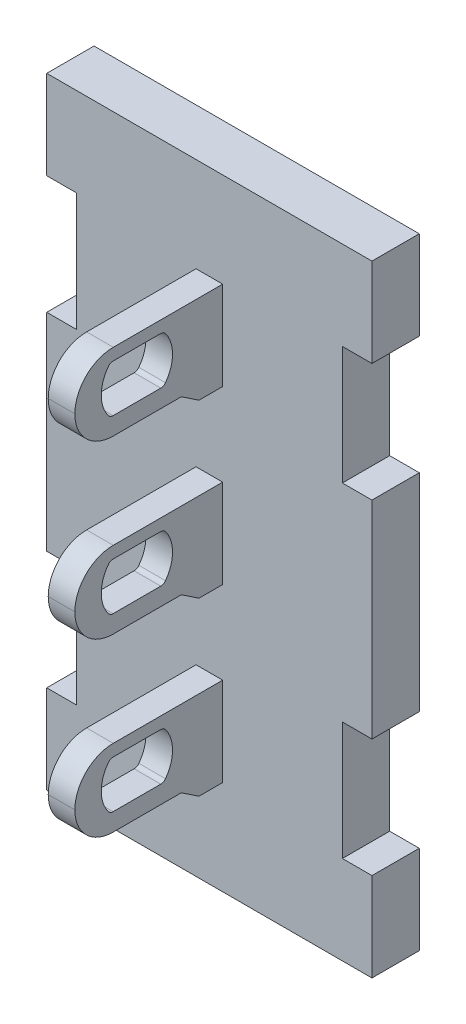
SolidWorks part; units mm, degrees
ref_plane "前视基准面" through (0, 0, 0) normal (0, 0, 1) x (1, 0, 0)
ref_plane "上视基准面" through (0, 0, 0) normal (0, 1, 0) x (1, 0, 0)
ref_plane "右视基准面" through (0, 0, 0) normal (1, 0, 0) x (0, 0, -1)
sketch "草图1" plane through (0, 0, 0) normal (0, 0, 1) x (1, 0, 0)
  line L1 (2.75, -5.25) -> (-2.75, -5.25)
  line L2 (2.75, -5.25) -> (2.75, 5.25)
  line L3 (2.75, 5.25) -> (-2.75, 5.25)
  line L4 (-2.75, -5.25) -> (-2.75, 5.25)
  line L5 (2.75, -5.25) -> (-2.75, 5.25) construction
  line L6 (2.75, 5.25) -> (-2.75, -5.25) construction
  point P0 (0, 0)
  dimension "D1" = 5.5
  dimension "D2" = 10.5
extrude "凸台-拉伸1" add sketch "草图1" along normal blind 0.8
sketch "草图2" plane through (0, 0, 0) normal (0, 0, -1) x (-1, 0, 0)
  line L0 (-2.75, -5.25) -> (-2.75, 5.25) construction
  line L1 (-2.25, 1.75) -> (-3.25, 1.75)
  line L2 (-2.25, 1.75) -> (-2.25, 3.75)
  line L3 (-2.25, 3.75) -> (-3.25, 3.75)
  line L4 (-3.25, 1.75) -> (-3.25, 3.75)
  line L5 (-2.25, 1.75) -> (-3.25, 3.75) construction
  line L6 (-2.25, 3.75) -> (-3.25, 1.75) construction
  line L7 (-2.75, 5.25) -> (2.75, 5.25) construction
  line L8 (2.75, -2.75) -> (-2.75, -2.75) construction
  line L9 (2.75, -2.75) -> (2.75, 2.75) construction
  line L10 (2.75, 2.75) -> (-2.75, 2.75) construction
  line L11 (-2.75, -2.75) -> (-2.75, 2.75) construction
  line L12 (2.75, -2.75) -> (-2.75, 2.75) construction
  line L13 (2.75, 2.75) -> (-2.75, -2.75) construction
  line L14 (-2.25, -3.75) -> (-3.25, -3.75)
  line L15 (-2.25, -3.75) -> (-2.25, -1.75)
  line L16 (-2.25, -1.75) -> (-3.25, -1.75)
  line L17 (-3.25, -3.75) -> (-3.25, -1.75)
  line L18 (-2.25, -3.75) -> (-3.25, -1.75) construction
  line L19 (-2.25, -1.75) -> (-3.25, -3.75) construction
  line L20 (2.25, -3.75) -> (3.25, -3.75)
  line L21 (2.25, -3.75) -> (2.25, -1.75)
  line L22 (2.25, -1.75) -> (3.25, -1.75)
  line L23 (3.25, -3.75) -> (3.25, -1.75)
  line L24 (2.25, -3.75) -> (3.25, -1.75) construction
  line L25 (2.25, -1.75) -> (3.25, -3.75) construction
  line L26 (3.25, 1.75) -> (2.25, 1.75)
  line L27 (3.25, 1.75) -> (3.25, 3.75)
  line L28 (3.25, 3.75) -> (2.25, 3.75)
  line L29 (2.25, 1.75) -> (2.25, 3.75)
  line L30 (3.25, 1.75) -> (2.25, 3.75) construction
  line L31 (3.25, 3.75) -> (2.25, 1.75) construction
  point P0 (-2.75, 2.75)
  point P7 (0, 0)
  dimension "D1" = 2
  dimension "D2" = 4.5
  dimension "D3" = 1.5
extrude "切除-拉伸1" cut sketch "草图2" against normal through all
sketch "草图3" plane through (0, 0, 0.8) normal (0, 0, 1) x (1, 0, 0)
  line L0 (0, 2.9) -> (0, 0) construction
  line L1 (0.225, 2.15) -> (-0.225, 2.15)
  line L2 (0.225, 2.15) -> (0.225, 3.65)
  line L3 (0.225, 3.65) -> (-0.225, 3.65)
  line L4 (-0.225, 2.15) -> (-0.225, 3.65)
  line L5 (0.225, 2.15) -> (-0.225, 3.65) construction
  line L6 (0.225, 3.65) -> (-0.225, 2.15) construction
  line L7 (0.225, -0.75) -> (-0.225, -0.75)
  line L8 (0.225, -0.75) -> (0.225, 0.75)
  line L9 (0.225, 0.75) -> (-0.225, 0.75)
  line L10 (-0.225, -0.75) -> (-0.225, 0.75)
  line L11 (0.225, -0.75) -> (-0.225, 0.75) construction
  line L12 (0.225, 0.75) -> (-0.225, -0.75) construction
  line L13 (0.225, -3.65) -> (-0.225, -3.65)
  line L14 (0.225, -3.65) -> (0.225, -2.15)
  line L15 (0.225, -2.15) -> (-0.225, -2.15)
  line L16 (-0.225, -3.65) -> (-0.225, -2.15)
  line L17 (0.225, -3.65) -> (-0.225, -2.15) construction
  line L18 (0.225, -2.15) -> (-0.225, -3.65) construction
  line L19 (0, 0) -> (0, -2.9) construction
  point P0 (0, 2.9)
  point P10 (0, -2.9)
  dimension "D1" = 1.5
  dimension "D2" = 7.3
  dimension "D3" = 0.45
extrude "凸台-拉伸2" add sketch "草图3" along normal blind 2.5
sketch "草图5" plane through (-0.225, 0, 0) normal (-1, 0, 0) x (0, 0, 1)
  line L0 (3.3, -3.65) -> (0.8, -3.65) construction
  line L1 (3.3, 2.15) -> (1.5, 2.15)
  line L2 (3.3, 2.15) -> (3.3, 2.35)
  line L3 (3.3, 2.35) -> (1.5, 2.35)
  line L4 (1.5, 2.15) -> (1.5, 2.35)
  line L5 (3.3, -0.75) -> (1.5, -0.75)
  line L6 (3.3, -0.75) -> (3.3, -0.55)
  line L7 (3.3, -0.55) -> (1.5, -0.55)
  line L8 (1.5, -0.75) -> (1.5, -0.55)
  line L9 (3.3, -3.65) -> (1.5, -3.65)
  line L10 (3.3, -3.65) -> (3.3, -3.45)
  line L11 (3.3, -3.45) -> (1.5, -3.45)
  line L12 (1.5, -3.65) -> (1.5, -3.45)
  line L13 (3.3, -2.15) -> (3.3, -3.65) construction
  line L14 (3.3, 3.65) -> (0.8, 3.65) construction
  line L15 (0.8, 3.65) -> (0.8, 2.15) construction
  dimension "D1" = 1.3
  dimension "D2" = 0.7
extrude "切除-拉伸2" cut sketch "草图5" against normal through all
fillet "圆角5" radius 0.65 6 edges at (0, -3.45, 3.3) (0, -2.15, 3.3) (0, -0.55, 3.3) (0, 0.75, 3.3) (0, 2.35, 3.3) (0, 3.65, 3.3)
chamfer "倒角1" distance 0.2 distance2 0.3 3 edges at (0, 2.15, 1.5) (0, -0.75, 1.5) (0, -3.65, 1.5) first distance on face at (0, 2.25, 1.5) first distance on face at (0, -0.65, 1.5) first distance on face at (0, -3.55, 1.5)
sketch "草图6" plane through (-0.225, 0, 0) normal (-1, 0, 0) x (0, 0, 1)
  line L0 (0.8, 3.75) -> (0.8, 1.75) construction
  line L1 (2.7, 2.65) -> (1.8, 2.65)
  line L2 (2.7, 2.65) -> (2.7, 3.45) construction
  line L3 (2.7, 3.45) -> (1.8, 3.45)
  line L4 (1.8, 2.65) -> (1.8, 3.45) construction
  line L5 (2.7, 2.65) -> (1.8, 3.45) construction
  line L6 (2.7, 3.45) -> (1.8, 2.65) construction
  arc A0 (1.8, 3.45) -> (1.8, 2.65) centre (2.2472, 3.05) ccw
  arc A1 (2.7, 3.45) -> (2.7, 2.65) centre (2.2528, 3.05) cw
  point P0 (2.25, 3.05)
  dimension "D1" = 0.6
  dimension "D2" = 0.8
  dimension "D3" = 0.05
  dimension "D4" = 0.9
  dimension "D5" = 1
extrude "切除-拉伸3" cut sketch "草图6" against normal through all
fillet "圆角6" radius 0.1 4 edges at (0, 3.45, 1.8) (0, 2.65, 1.8) (0, 2.65, 2.7) (0, 3.45, 2.7)
pattern_linear "阵列(线性)1" count 3 spacing 2.9 along (0, -1, 0) of "圆角6", "切除-拉伸3"
extrude "凸台-拉伸3" add sketch "草图3<2>" against normal blind 1.4
sketch "草图3<2>" plane through (0, 0, 0.8) normal (0, 0, 1) x (1, 0, 0) same geometry as "草图3"
sketch "草图8" plane through (-0.225, 0, 0) normal (-1, 0, 0) x (0, 0, 1)
  line L0 (-0.6, 3.65) -> (-0.6, 2.15) construction
  line L1 (-0.1, -4.15) -> (-0.6, -4.15)
  line L2 (-0.1, -4.15) -> (-0.1, -1.65)
  line L3 (-0.1, -1.65) -> (-0.6, -1.65)
  line L4 (-0.6, -4.15) -> (-0.6, -1.65)
  line L5 (-0.1, -4.15) -> (-0.6, -1.65) construction
  line L6 (-0.1, -1.65) -> (-0.6, -4.15) construction
  line L7 (-0.1, 4.15) -> (-0.6, 4.15)
  line L8 (-0.1, 4.15) -> (-0.1, 1.65)
  line L9 (-0.1, 1.65) -> (-0.6, 1.65)
  line L10 (-0.6, 4.15) -> (-0.6, 1.65)
  line L11 (-0.1, 4.15) -> (-0.6, 1.65) construction
  line L12 (-0.1, 1.65) -> (-0.6, 4.15) construction
  line L14 (-0.35, -2.9) -> (0, -2.9) construction
  line L15 (0, -2.15) -> (0, -3.65) construction
  line L16 (0, 0) -> (-0.6, 0) construction
  line L17 (-0.6, 0.75) -> (-0.6, -0.75) construction
  line L18 (-0.6, -1.25) -> (-0.1, -1.25)
  line L19 (-0.1, -1.25) -> (-0.1, 1.25)
  line L20 (-0.1, 1.25) -> (-0.6, 1.25)
  arc A0 (-0.6, -1.25) -> (-0.6, 1.25) centre (0.9612, 0) cw
  point P0 (-0.35, -2.9)
  point P5 (-0.35, 2.9)
  point P28 (-0.1, 0)
  dimension "D3" = 2
  dimension "D1" = 0.5
  dimension "D2" = 2.5
extrude "凸台-拉伸4" add sketch "草图8" against normal blind 0.45
